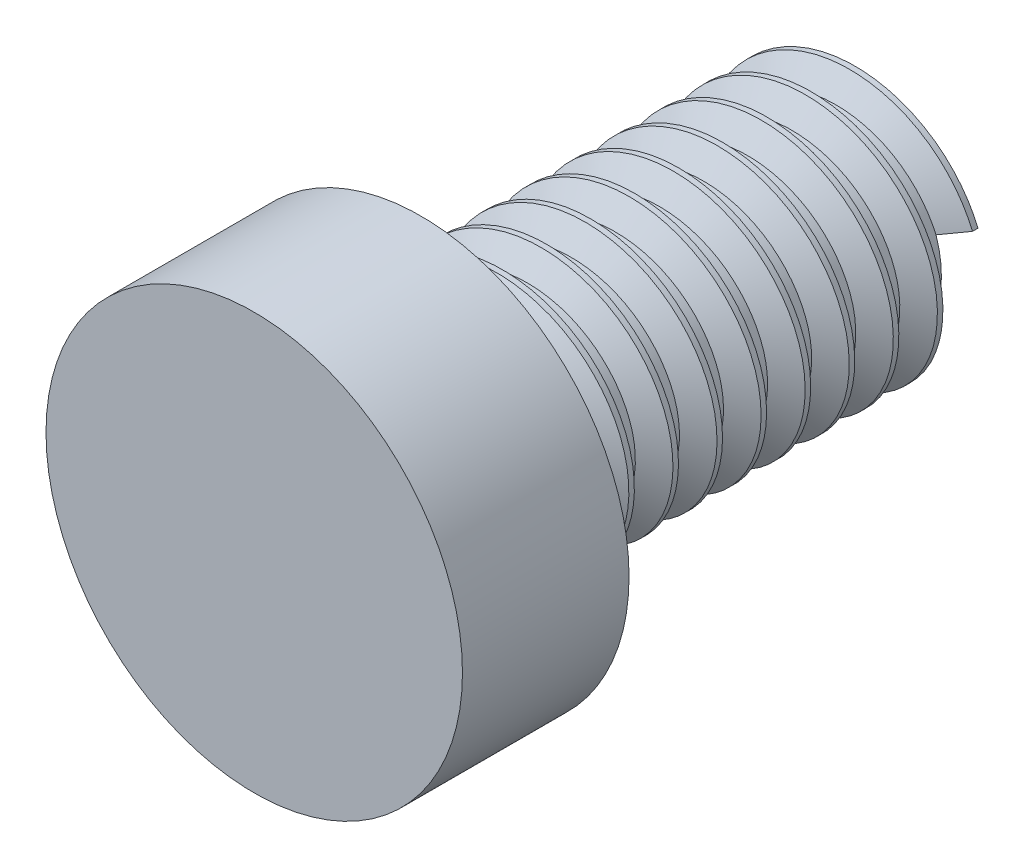
SolidWorks part; units mm, degrees
ref_plane "Front Plane" through (0, 0, 0) normal (0, 0, 1) x (1, 0, 0)
ref_plane "Top Plane" through (0, 0, 0) normal (0, 1, 0) x (1, 0, 0)
ref_plane "Right Plane" through (0, 0, 0) normal (1, 0, 0) x (0, 0, -1)
sketch "Sketch1" plane through (0, 0, 0) normal (0, 0, 1) x (1, 0, 0)
  circle A0 centre (0, 0) radius 2.5
  dimension "D1" = 5
extrude "Boss-Extrude1" add sketch "Sketch1" along normal blind 10
thread "Thread1" pitch 1.0583 method extrude profile "Thread Profile1" start angle 0, offset 0, length 10, pitch 1.0583, diameter 5
ref_plane "Plane1" through (-2.5, 0, 10) normal (0, -1, 0) x (-1, 0, 0)
sketch "Thread Profile1" plane through (-2.5, 0, 10) normal (0, -1, 0) x (-1, 0, 0)
  line L0 (0, 0) -> (0, 1.0583) construction
  line L1 (0, 0) -> (0.5728, 0.3307)
  line L2 (0.5728, 0.3307) -> (0.5728, 0.463)
  line L3 (0.5728, 0.463) -> (0, 0.7937)
  line L4 (0.5728, 0.3969) -> (0, 0.3969) construction
  line L11 (0, 0) -> (0, 0.7937)
  point P2 (0, 0)
  dimension "Pitch" = 1.0583
  dimension "Profile_Angle" = 60
  dimension "Profile_Land" = 0.1323
  dimension "Profile_Height" = 0.5728
sketch "Sketch4" plane through (0, 0, 10) normal (0, 0, 1) x (1, 0, 0)
  circle A0 centre (0, 0) radius 5
  point P3 (0, 0)
  dimension "D1" = 10
extrude "Boss-Extrude2" add sketch "Sketch4" along normal blind 4
